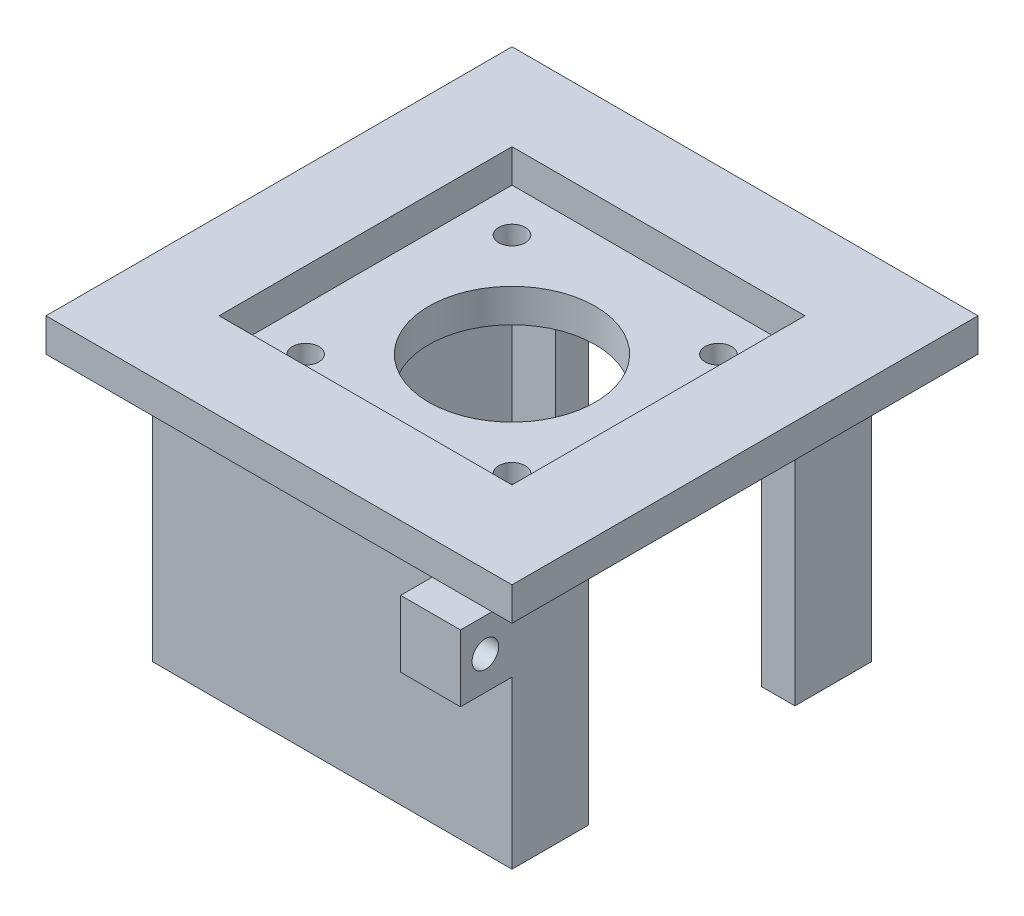
SolidWorks part; units mm, degrees
ref_plane "Спереди" through (0, 0, 0) normal (0, 0, 1) x (1, 0, 0)
ref_plane "Сверху" through (0, 0, 0) normal (0, 1, 0) x (1, 0, 0)
ref_plane "Справа" through (0, 0, 0) normal (1, 0, 0) x (0, 0, -1)
sketch "Эскиз1" plane through (0, 0, 0) normal (0, 1, 0) x (1, 0, 0)
  line L1 (22, -22) -> (22, 22)
  line L2 (22, 22) -> (-22, 22)
  line L3 (-22, 22) -> (-22, -22)
  line L4 (-22, -22) -> (22, -22)
  line L5 (28, 22) -> (28, 28) construction
  line L7 (28, 28) -> (-28, 28)
  line L8 (28, 28) -> (28, -28)
  line L9 (28, -28) -> (-28, -28)
  line L10 (-28, 28) -> (-28, -28)
  point P4 (0, 0)
  point P7 (22, 0)
  point P12 (0, 0)
  dimension "D1" = 56
  dimension "D2" = 44
extrude "Бобышка-Вытянуть1" add sketch "Эскиз1" along normal blind 10 and the other way blind 35
sketch "Эскиз3" plane through (0, 0, 0) normal (0, 1, 0) x (1, 0, 0)
  line L0 (28, 28) -> (-28, -28) construction
  line L3 (28, -28) -> (-28, 28) construction
  line L4 (27, -27) -> (-27, -27)
  line L5 (27, -27) -> (27, 27)
  line L6 (27, 27) -> (-27, 27)
  line L7 (-27, -27) -> (-27, 27)
  line L8 (27, -27) -> (-27, 27) construction
  line L9 (27, 27) -> (-27, -27) construction
  line L10 (35, -35) -> (-35, -35)
  line L11 (35, -35) -> (35, 35)
  line L12 (35, 35) -> (-35, 35)
  line L13 (-35, -35) -> (-35, 35)
  line L14 (35, -35) -> (-35, 35) construction
  line L15 (35, 35) -> (-35, -35) construction
  point P3 (0, 0)
  point P15 (0, 0)
  dimension "D1" = 70
  dimension "D2" = 54
extrude "Бобышка-Вытянуть2" add sketch "Эскиз3" along normal blind 10
extrude "Вырез-Вытянуть1" cut sketch "Эскиз3<2>" against normal blind 40 and the other way blind 5
sketch "Эскиз3<2>" plane through (0, 0, 0) normal (0, 1, 0) x (1, 0, 0) same geometry as "Эскиз3"
sketch "Эскиз4" plane through (0, 0, 0) normal (0, 1, 0) x (1, 0, 0)
  line L1 (-23.5348, 24.7169) -> (24.0722, 24.7169)
  line L2 (-23.5348, 24.7169) -> (-23.5348, -23.7498)
  line L3 (-23.5348, -23.7498) -> (24.0722, -23.7498)
  line L4 (24.0722, 24.7169) -> (24.0722, -23.7498)
  line L5 (-15.5, -15.5) -> (15.5, -15.5) construction
  line L6 (-15.5, -15.5) -> (-15.5, 15.5) construction
  line L7 (-15.5, 15.5) -> (15.5, 15.5) construction
  line L8 (15.5, -15.5) -> (15.5, 15.5) construction
  line L9 (-15.5, -15.5) -> (15.5, 15.5) construction
  line L10 (-15.5, 15.5) -> (15.5, -15.5) construction
  circle A0 centre (0, 0) radius 12.5
  circle A1 centre (-15.5, 15.5) radius 2
  circle A2 centre (-15.5, -15.5) radius 2
  circle A3 centre (15.5, -15.5) radius 2
  circle A4 centre (15.5, 15.5) radius 2
  dimension "D1" = 4
  dimension "D2" = 25
extrude "Бобышка-Вытянуть3" add sketch "Эскиз4" along normal blind 5
sketch "Эскиз5" plane through (0, 0, 0) normal (0, 1, 0) x (1, 0, 0)
  line L0 (-15.5, -15.5) -> (45.9042, -15.5)
  line L1 (-15.5, -15.5) -> (-15.5, 51.8109)
  line L2 (15.5, 15.5) -> (45.9042, 15.5)
  line L3 (15.5, 15.5) -> (15.5, 51.8109)
  line L4 (15.5, 51.8109) -> (-15.5, 51.8109)
  line L5 (45.9042, 15.5) -> (45.9042, -15.5)
extrude "Вырез-Вытянуть2" cut sketch "Эскиз5" against normal blind 50
sketch "Эскиз6" plane through (0, 0, 0) normal (0, 1, 0) x (1, 0, 0)
  line L0 (0, 0) -> (0, 28) construction
  line L1 (-22.1364, 27) -> (-34.6364, 27)
  line L2 (-34.6364, 27) -> (-34.6364, 18)
  line L3 (-34.6364, 18) -> (-22.1364, 18)
  line L5 (0, 0) -> (28, 0) construction
  line L6 (27, -22.2344) -> (27, -34.7344)
  line L7 (27, -34.7344) -> (18, -34.7344)
  line L8 (18, -34.7344) -> (18, -22.2344)
  line L10 (18, -22.2344) -> (27, -22.2344)
  line L11 (-22.1364, 18) -> (-22.1364, 27)
  point P2 (0, 0)
  point P10 (0, 0)
  point P14 (0, 0)
  point P15 (0, 0)
extrude "Бобышка-Вытянуть4" add sketch "Эскиз6" against normal blind 10
sketch "Эскиз7" plane through (0, 0, 0) normal (1, 0, 0) x (0, 0, -1)
  line L0 (0, 0) -> (-31, 0) construction
  line L2 (-31, 0) -> (-31, -5) construction
  line L4 (-22, 0) -> (22, 0) construction
  circle A0 centre (-31, -5) radius 2
extrude "Вырез-Вытянуть3" cut sketch "Эскиз7" along normal blind 1000
sketch "Эскиз8" plane through (0, 0, 0) normal (0, 0, 1) x (1, 0, 0)
  line L0 (0, 0) -> (-31, 0) construction
  line L1 (-27, 0) -> (-34.6364, 0) construction
  line L2 (-31, 0) -> (-31, -5) construction
  circle A0 centre (-31, -5) radius 2
extrude "Вырез-Вытянуть4" cut sketch "Эскиз8" against normal blind 1000
